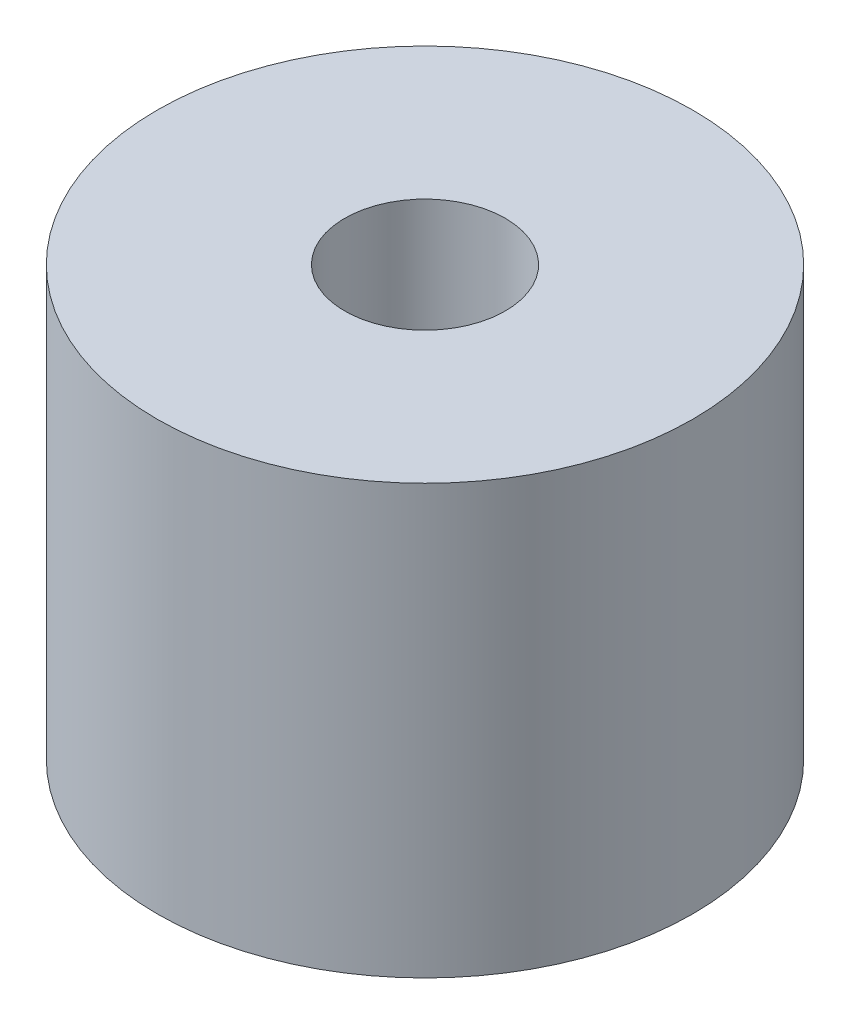
SolidWorks part; units mm, degrees
ref_plane "Front Plane" through (0, 0, 0) normal (0, 0, 1) x (1, 0, 0)
ref_plane "Top Plane" through (0, 0, 0) normal (0, 1, 0) x (1, 0, 0)
ref_plane "Right Plane" through (0, 0, 0) normal (1, 0, 0) x (0, 0, -1)
sketch "Sketch1" plane through (0, 0, 0) normal (0, 1, 0) x (1, 0, 0)
  circle A0 centre (0, 0) radius 25
  dimension "D1" = 50
base flange "Base-Flange1" sketch "Sketch1" thickness 40 reverse thickness direction no parameters "D1"=5
sketch "Sketch8" plane through (0, -40, 0) normal (0, -1, 0) x (1, 0, 0)
  circle A0 centre (0, 0) radius 11
  dimension "D1" = 22
extrude "Cut-Extrude2" cut sketch "Sketch8" against normal blind 5 normal cut yes
sketch "Sketch9" plane through (0, -35, 0) normal (0, -1, 0) x (1, 0, 0)
  circle A0 centre (0, 0) radius 7.5
  dimension "D1" = 15
extrude "Cut-Extrude3" cut sketch "Sketch9" against normal through all normal cut yes
sketch "Bend-Lines1" [suppressed] plane through (0, 0, 0) normal (0, 1, 0) x (1, 0, 0)
sketch "Bounding-Box1" [suppressed] plane through (0, 0, 0) normal (0, 1, 0) x (1, 0, 0)
sheet metal parameters "Sheet-Metal1" thickness 40 parameters "D1"=5
flat pattern "Flat-Pattern1" [suppressed]
sketch "Bend-Lines2" plane through (0, 0, 0) normal (0, 1, 0) x (1, 0, 0)
sketch3d "Bounding-Box2" [suppressed]
  line L0 (15.0499, -14.9498, 0) -> (-14.9499, -15.0498, 0) construction
  line L1 (14.9499, 15.0499, 0) -> (-15.0499, 14.9499, 0) construction
  line L2 (15.0499, -14.9498, 0) -> (14.9499, 15.0499, 0) construction
  line L3 (-14.9499, -15.0498, 0) -> (-15.0499, 14.9499, 0) construction
sheet metal parameters "Sheet-Metal3" thickness 40 parameters "D1"=5
flat pattern "Flat-Pattern1"
sketch "Bend-Lines2" plane through (0, 0, 0) normal (0, 1, 0) x (1, 0, 0)
sketch3d "Bounding-Box2" [suppressed]
  line L0 (15.0499, -14.9498, 0) -> (-14.9499, -15.0498, 0) construction
  line L1 (14.9499, 15.0499, 0) -> (-15.0499, 14.9499, 0) construction
  line L2 (15.0499, -14.9498, 0) -> (14.9499, 15.0499, 0) construction
  line L3 (-14.9499, -15.0498, 0) -> (-15.0499, 14.9499, 0) construction
sheet metal parameters "Sheet-Metal4" thickness 40 parameters "D1"=5
flat pattern "Flat-Pattern1"
sketch "Bend-Lines2" plane through (0, 0, 0) normal (0, 1, 0) x (1, 0, 0)
sketch3d "Bounding-Box2" [suppressed]
  line L0 (-25.0403, 24.9596, 0) -> (-24.9596, -25.0403, 0) construction
  line L1 (24.9596, 25.0403, 0) -> (25.0403, -24.9596, 0) construction
  line L2 (-25.0403, 24.9596, 0) -> (24.9596, 25.0403, 0) construction
  line L3 (-24.9596, -25.0403, 0) -> (25.0403, -24.9596, 0) construction
